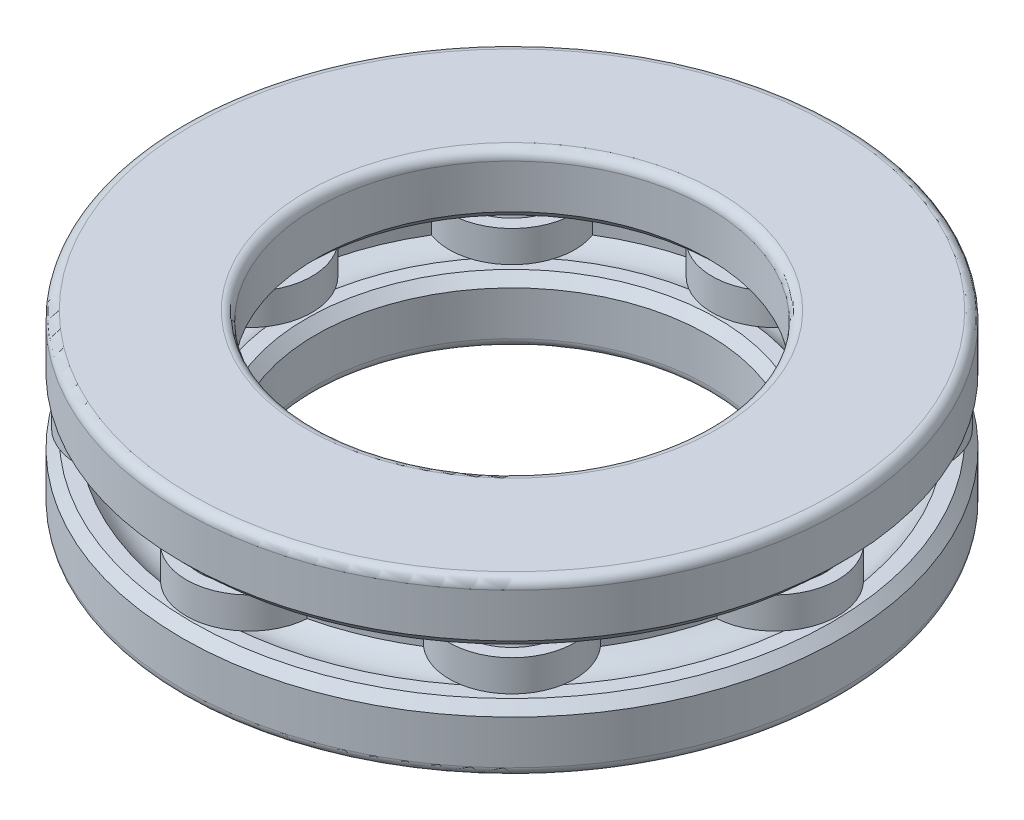
SolidWorks part; units mm, degrees
ref_plane "Front Plane" through (0, 0, 0) normal (0, 0, 1) x (1, 0, 0)
ref_plane "Top Plane" through (0, 0, 0) normal (0, 1, 0) x (1, 0, 0)
ref_plane "Right Plane" through (0, 0, 0) normal (1, 0, 0) x (0, 0, -1)
sketch "Sketch1" plane through (0, 0, 0) normal (1, 0, 0) x (0, 0, -1)
  line L0 (0, 0) -> (0, 11.4419) construction
  line L1 (0, 0) -> (-16.75, 0) construction
  line L2 (-16.75, 0) -> (-16.75, 9.5826) construction
  line L3 (-16.75, 3) -> (-16.75, -3)
  line L4 (-12.5, 0) -> (-12.5, -11.7804) construction
  line L5 (-21, 0) -> (-21, -11.35) construction
  line L6 (-21, -5.675) -> (-12.5, -5.675) construction
  arc A0 (-16.75, 3) -> (-16.75, -3) centre (-16.75, 0) ccw
  point P13 (-16.75, -5.675)
  dimension "D1" = 33.5
  dimension "D2" = 6
  dimension "D3" = 12.5
  dimension "D4" = 21
revolve "Revolve4" add sketch "Sketch1" angle 360 about L2
sketch "Sketch3" plane through (0, 0, 0) normal (1, 0, 0) x (0, 0, -1)
  line L0 (0, 0) -> (0, 7.9818) construction
  line L1 (-21, 5.5) -> (-21, 1.5)
  line L2 (-21, 1.5) -> (-12.5, 1.5)
  line L3 (-12.5, 1.5) -> (-12.5, 5.5)
  line L4 (0, 0) -> (0, -6.0195) construction
  line L5 (-12.5, 5.5) -> (-21, 5.5)
  line L6 (-21, -1.5) -> (-12.5, -1.5)
  line L7 (-12.5, -1.5) -> (-12.5, -5.5)
  line L8 (-12.5, -5.5) -> (-21, -5.5)
  line L9 (-21, -5.5) -> (-21, -1.5)
  line L10 (-12.5, 1.5) -> (-12.5, -1.5) construction
  line L11 (-12.5, 0) -> (0, 0) construction
  circle A0 centre (-16.75, 0) radius 3 construction
  circle A1 centre (-16.75, 0) radius 3
  circle A2 centre (-16.75, 0) radius 3.1
  dimension "D5" = 6
  dimension "D1" = 11
  dimension "D2" = 25
  dimension "D3" = 42
  dimension "D4" = 4
  dimension "D6" = 0.1
revolve "Revolve5" add sketch "Sketch3" angle 360 about L0 region at (0, 3.7979, 16.75) region at (0, -3.7979, 16.75)
pattern_circular "CirPattern2" count 8 over 360 about axis through (0, 5.5, 0) along (0, -1, 0) of bodies 101
fillet "Fillet1" radius 0.6 2 edges at (0, 5.5, -12.5) (0, 5.5, -21)
chamfer "Chamfer1" distance 0.6 angle 45 2 edges at (0, -1.5, -12.5) (0, -1.5, -21)
fillet "Fillet2" radius 0.6 2 edges at (0, -5.5, -12.5) (0, -5.5, -21)
chamfer "Chamfer2" distance 0.6 angle 45 2 edges at (0, 1.5, -12.5) (0, 1.5, -21)
sketch "Sketch4" plane through (0, 0, 0) normal (0, 1, 0) x (1, 0, 0)
  circle A1 centre (-16.75, 0) radius 4
  circle A2 centre (-16.75, 0) radius 3.2
  circle A3 centre (-16.75, 0) radius 3.2
  circle A4 centre (-11.844, 11.844) radius 4
  circle A5 centre (-11.844, 11.844) radius 3.2
  circle A6 centre (0, 16.75) radius 4
  circle A7 centre (0, 16.75) radius 3.2
  circle A8 centre (11.844, 11.844) radius 4
  circle A9 centre (11.844, 11.844) radius 3.2
  circle A10 centre (16.75, 0) radius 4
  circle A11 centre (16.75, 0) radius 3.2
  circle A12 centre (11.844, -11.844) radius 4
  circle A13 centre (11.844, -11.844) radius 3.2
  circle A14 centre (0, -16.75) radius 4
  circle A15 centre (0, -16.75) radius 3.2
  circle A16 centre (-11.844, -11.844) radius 4
  circle A17 centre (-11.844, -11.844) radius 3.2
  circle A18 centre (0, 0) radius 15.5
  circle A19 centre (0, 0) radius 17.5
  point P35 (0, 0)
  dimension "D4" = 31
  dimension "D5" = 35
  dimension "D1" = 0.2
  dimension "D2" = 0.8
  dimension "D3" = 8
extrude "Boss-Extrude1" add sketch "Sketch4" along normal blind 1 and the other way blind 1 separate body contours A16 A19 A14 A18 | A16 A18 A17 | A17 A19 A16 A18 | A19 A16 A17 | A16 A19 A17 A18 | A1 A19 A16 A18 | A1 A18 A3 | A3 A19 A1 A18 | A19 A1 A3 | A1 A19 A3 A18 | A4 A19 A1 A18 | A5 A19 A4 A18 | A19 A4 A5 | A4 A18 A5 | A4 A19 A5 A18 | A6 A19 A4 A18 | A6 A18 A7 | A6 A19 A7 A18 | A19 A6 A7 | A7 A19 A6 A18 | A8 A19 A9 A18 | A8 A18 A9 | A19 A8 A9 | A9 A19 A8 A18 | A8 A19 A6 A18 | A10 A18 A11 | A11 A19 A10 A18 | A10 A19 A11 A18 | A19 A10 A11 | A10 A19 A8 A18 | A12 A19 A10 A18 | A13 A19 A12 A18 | A12 A18 A13 | A19 A12 A13 | A12 A19 A13 A18 | A14 A19 A12 A18 | A15 A19 A14 A18 | A15 A18 A14 | A19 A15 A14 | A14 A19 A15 A18 region at (-13.4439, 0, 2.1123) region at (-16.1267, 0, -3.4969) region at (-15.2087, 0, -6.2997) region at (-15.2087, 0, 6.2997) region at (-16.1267, 0, 3.4969) region at (-17.2162, 0, -3.5971) region at (-12.938, 0, -8.3968) region at (-13.876, 0, -8.9306) region at (-13.876, 0, 8.9306) region at (-9.5976, 0, 8.6268) region at (-14.6063, 0, -14.6063) region at (-14.7219, 0, 9.6332) region at (-6.2997, 0, -15.2087) region at (-8.9306, 0, -13.876) region at (-8.9306, 0, 13.876) region at (-6.2997, 0, 15.2087) region at (-3.4969, 0, -16.1267) region at (0, 0, -20.662) region at (-3.2109, 0, -15.0853) region at (-3.5971, 0, 17.2162) region at (-3.4969, 0, 16.1267) region at (0, 0, 12.8267) region at (6.2997, 0, -15.2087) region at (3.4969, 0, -16.1267) region at (3.4969, 0, 16.1267) region at (6.2997, 0, 15.2087) region at (8.9306, 0, -13.876) region at (13.4685, 0, -15.3967) region at (8.3968, 0, -12.938) region at (9.6332, 0, 14.7219) region at (8.9306, 0, 13.876) region at (9.0694, 0, 9.0694) region at (13.876, 0, -8.9306) region at (15.2087, 0, -6.2997) region at (15.2087, 0, 6.2997) region at (13.876, 0, 8.9306) region at (15.0853, 0, -3.2109) region at (16.1267, 0, -3.4969) region at (16.1267, 0, 3.4969) region at (19.6144, 0, -2.6643)
